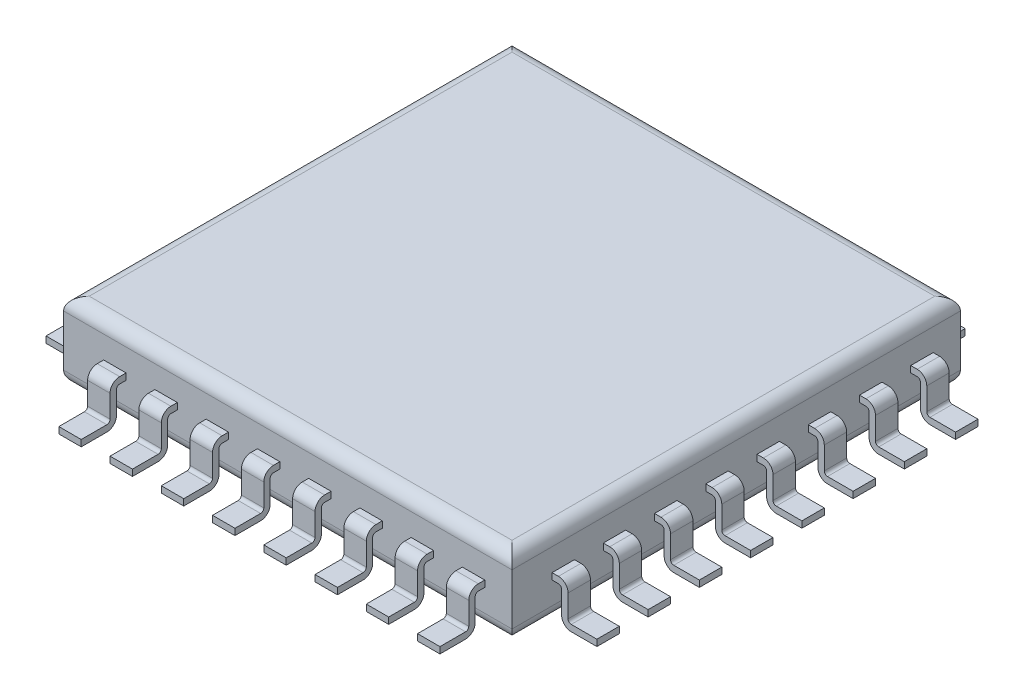
SolidWorks part; units mm, degrees
ref_plane "Front" through (0, 0, 0) normal (0, 0, 1) x (1, 0, 0)
ref_plane "Top" through (0, 0, 0) normal (0, 1, 0) x (1, 0, 0)
ref_plane "Right" through (0, 0, 0) normal (1, 0, 0) x (0, 0, -1)
sketch "Sketch1" plane through (0, 0, 0) normal (0, 1, 0) x (1, 0, 0)
  line L1 (-3.5, -3.5) -> (3.5, -3.5)
  line L2 (-3.5, -3.5) -> (-3.5, 3.5)
  line L3 (-3.5, 3.5) -> (3.5, 3.5)
  line L4 (3.5, -3.5) -> (3.5, 3.5)
  line L5 (-3.5, -3.5) -> (3.5, 3.5) construction
  line L6 (-3.5, 3.5) -> (3.5, -3.5) construction
  point P0 (0, 0)
  dimension "D1" = 7
  dimension "D2" = 7
extrude "Boss-Extrude1" add sketch "Sketch1" along normal blind 1.2
fillet "Fillet1" radius 0.2 8 edges at (0, 0, -3.5) (-3.5, 0, 0) (0, 0, 3.5) (3.5, 0, 0) (0, 1.2, -3.5) (3.5, 1.2, 0) (0, 1.2, 3.5) (-3.5, 1.2, 0)
ref_plane "Plane1" through (0, 0, -2.7) normal (0, 0, -1) x (-1, 0, 0)
sketch "Sketch2" plane through (0, 0, -2.7) normal (0, 0, -1) x (-1, 0, 0)
  line L0 (3.5, 0.6) -> (3.6, 0.6)
  line L1 (3.7, 0.5) -> (3.7, 0.15)
  line L2 (3.8, 0.05) -> (4.2, 0.05)
  line L3 (3.5, 1) -> (3.5, 0.2) construction
  line L4 (-3.3, 0) -> (3.3, 0) construction
  arc A0 (3.7, 0.15) -> (3.8, 0.05) centre (3.8, 0.15) ccw
  arc A1 (3.6, 0.6) -> (3.7, 0.5) centre (3.6, 0.5) cw
  point P10 (3.7, 0.05)
  point P13 (3.7, 0.6)
  dimension "D4" = 0.1
  dimension "D1" = 0.2
  dimension "D2" = 0.05
  dimension "D3" = 0.5
sketch "Sketch3" plane through (-3.5, 0, 0) normal (-1, 0, 0) x (0, 0, 1)
  line L1 (-2.875, 0.55) -> (-2.525, 0.55)
  line L2 (-2.875, 0.55) -> (-2.875, 0.65)
  line L3 (-2.875, 0.65) -> (-2.525, 0.65)
  line L4 (-2.525, 0.55) -> (-2.525, 0.65)
  line L5 (-2.875, 0.55) -> (-2.525, 0.65) construction
  line L6 (-2.875, 0.65) -> (-2.525, 0.55) construction
  point P0 (-2.7, 0.6)
  dimension "D1" = 0.1
  dimension "D2" = 0.35
sweep "Sweep1" add profiles "Sketch3" path "Sketch2"
pattern_linear "LPattern1" count 8 spacing 0.8 along (0, 0, 1) of "Sweep1"
ref_axis "Axis1" through (0, 50, 0) along (0, -1, 0)
pattern_circular "CirPattern1" count 4 over 360 about axis through (0, 50, 0) along (0, -1, 0) of "LPattern1"
